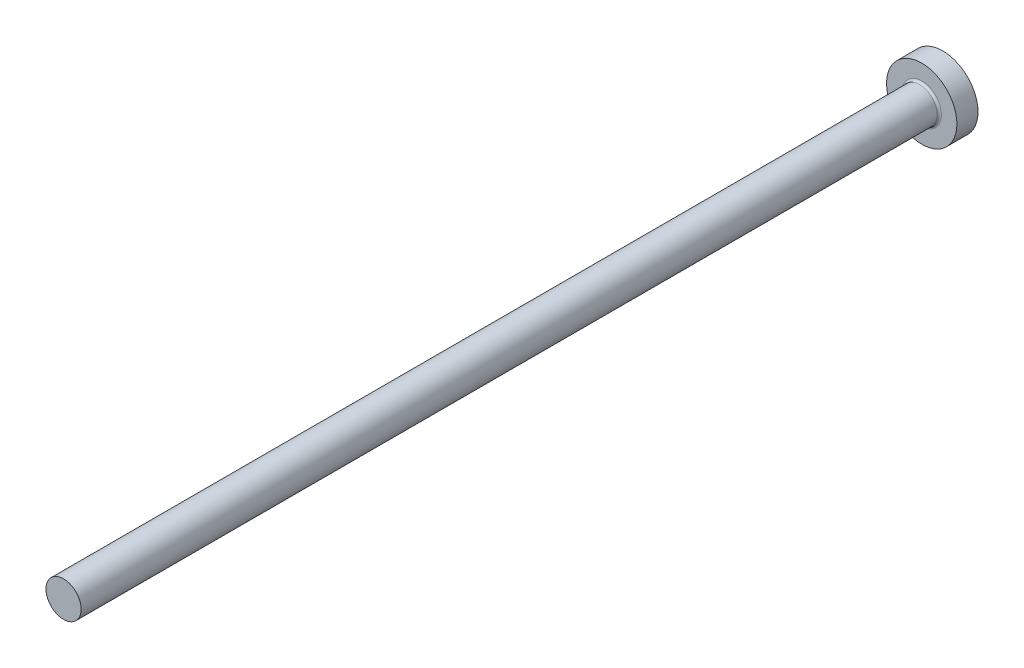
SolidWorks part; units mm, degrees
ref_plane "Płaszczyzna przednia" through (0, 0, 0) normal (0, 0, 1) x (1, 0, 0)
ref_plane "Płaszczyzna górna" through (0, 0, 0) normal (0, 1, 0) x (1, 0, 0)
ref_plane "Płaszczyzna prawa" through (0, 0, 0) normal (1, 0, 0) x (0, 0, -1)
sketch "Szkic1" plane through (0, 0, 0) normal (1, 0, 0) x (0, 0, -1)
  line L0 (-3, 0) -> (-3, 5)
  line L1 (-3, 5) -> (0, 5)
  line L2 (0, 5) -> (0, 0)
  line L3 (0, 0) -> (-3, 0)
  line L4 (0, 0) -> (-3, 0) construction
sketch "Szkic2" plane through (0, 0, 0) normal (1, 0, 0) x (0, 0, -1)
  line L0 (-125, 0) -> (-125, 2.5)
  line L1 (-125, 2.5) -> (-3, 2.5)
  line L2 (-3, 2.5) -> (-3, 0)
  line L3 (-3, 0) -> (-125, 0)
  line L4 (-3, 0) -> (-125, 0) construction
sketch "Szkic3" plane through (0, 0, 0) normal (1, 0, 0) x (0, 0, -1)
  line L0 (-3.3, 2.5) -> (-3, 2.5)
  line L1 (-3, 2.5) -> (-3, 2.8)
  line L2 (0, 0) -> (-3, 0) construction
  arc A0 (-3, 2.8) -> (-3.3, 2.5) centre (-3.3, 2.8) cw
revolve "Obrót1" add sketch "Szkic1" angle 360 about L4 reverse direction yes
revolve "Obrót2" add sketch "Szkic2" angle 360 about L4 reverse direction yes
revolve "Obrót3" add sketch "Szkic3" angle 360 about L2 reverse direction yes
ref_plane "IP1 XY" through (0, 0, 0) normal (0, 0, 1) x (1, 0, 0)
ref_plane "IP1 XZ" through (0, 0, 0) normal (0, -1, 0) x (-1, 0, 0)
ref_plane "IP1 YZ" through (0, 0, 0) normal (1, 0, 0) x (0, 0, -1)
ref_axis "IP1 X" through (-80.9, 0, 0) along (1, 0, 0)
ref_axis "IP1 Y" through (0, -50, 0) along (0, 1, 0)
ref_axis "IP1 Z" through (0, 0, 80.9) along (0, 0, -1)
sketch3d "IP1"
  point P0 (0, 0, 0)
